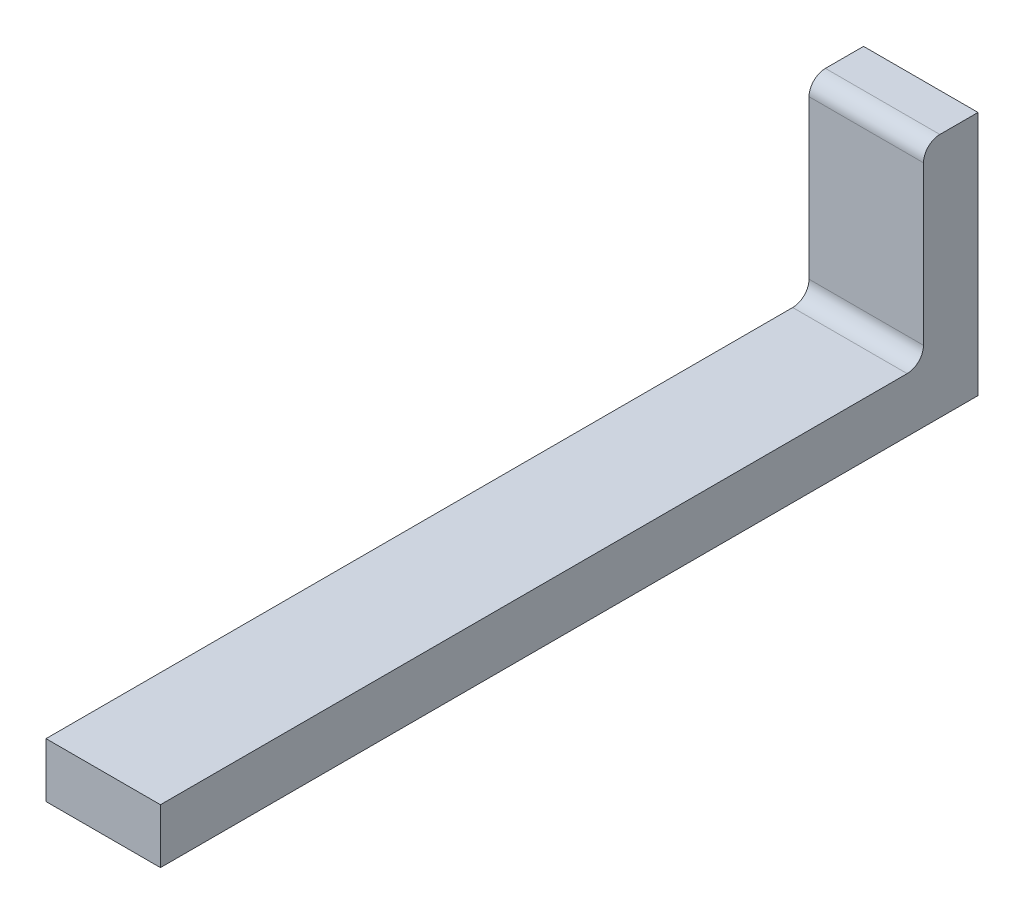
SolidWorks part; units mm, degrees
ref_plane "Front Plane" through (0, 0, 0) normal (0, 0, 1) x (1, 0, 0)
ref_plane "Top Plane" through (0, 0, 0) normal (0, 1, 0) x (1, 0, 0)
ref_plane "Right Plane" through (0, 0, 0) normal (1, 0, 0) x (0, 0, -1)
sketch "Sketch1" plane through (0, 0, 0) normal (0, 1, 0) x (1, 0, 0)
  line L1 (-41, -75) -> (41, -75)
  line L2 (-41, -75) -> (-41, 75)
  line L3 (-41, 75) -> (41, 75)
  line L4 (41, -75) -> (41, 75)
  line L5 (-41, -75) -> (41, 75) construction
  line L6 (-41, 75) -> (41, -75) construction
  point P0 (0, 0)
  dimension "D1" = 82
  dimension "D2" = 150
extrude "Boss-Extrude1" add sketch "Sketch1" along normal blind 10
sketch "Sketch2" plane through (41, 0, 0) normal (1, 0, 0) x (0, 0, -1)
  line L1 (75, 0) -> (65, 0)
  line L2 (75, 0) -> (75, 45)
  line L3 (75, 45) -> (65, 45)
  line L4 (65, 0) -> (65, 45)
  dimension "D1" = 10
  dimension "D2" = 45
extrude "Boss-Extrude2" add sketch "Sketch2" against normal through all
sketch "Sketch3" plane through (0, 0, -65) normal (0, 0, 1) x (1, 0, 0)
  line L0 (-41, 45) -> (41, 45) construction
  line L2 (10, 45) -> (10, 10)
  line L3 (10, 10) -> (20, 10)
  line L4 (20, 45) -> (20, 10)
  line L5 (-41, 10) -> (41, 10) construction
  line L6 (41, 45) -> (41, 10) construction
  line L7 (0, -55) -> (0, 55) construction
  line L9 (10, 45) -> (10, 87)
  line L10 (10, 87) -> (20, 87)
  line L11 (20, 45) -> (20, 87)
  line L12 (-10, 45) -> (-10, 87)
  line L13 (-10, 87) -> (-20, 87)
  line L14 (-20, 45) -> (-20, 87)
  line L15 (-20, 45) -> (-20, 10)
  line L16 (-10, 10) -> (-20, 10)
  line L17 (-10, 45) -> (-10, 10)
  dimension "D1" = 21
  dimension "D2" = 10
  dimension "D3" = 42
extrude "Boss-Extrude3" add sketch "Sketch3" along normal blind 42 and the other way blind 10
fillet "Fillet3" 2 edges at (15, 87, -23) (15, 87, -75) type full round first side face at (15, 48.5, -23) second side face at (0, 51.5, -75) middle face at (15, 87, -49)
fillet "Fillet4" 2 edges at (-15, 87, -23) (-15, 87, -75) type full round first side face at (-15, 48.5, -23) second side face at (0, 47.1667, -75) middle face at (-15, 87, -49)
sketch "Sketch4" plane through (20, 0, 0) normal (1, 0, 0) x (0, 0, -1)
  line L0 (23, 10) -> (23, 50)
  line L1 (23, 10) -> (23, 61) construction
  line L2 (23, 50) -> (-75, 25)
  line L3 (-75, 25) -> (-75, 10)
  line L4 (-75, 10) -> (23, 10)
  dimension "D1" = 15
  dimension "D2" = 40
extrude "Boss-Extrude4" add sketch "Sketch4" against normal up to surface (10 mm away) up to face at (10, 43, -54.3333)
sketch "Sketch5" plane through (-20, 0, 0) normal (-1, 0, 0) x (0, 0, 1)
  line L0 (-23, 50) -> (75, 25)
  line L1 (75, 25) -> (75, 10)
  line L2 (75, 10) -> (-23, 10)
  line L3 (-23, 10) -> (-23, 50)
extrude "Boss-Extrude5" add sketch "Sketch5" against normal up to surface (10 mm away) up to face at (-10, 43, -54.3333)
fillet "Fillet5" radius 15 1 edges at (15, 25, 75)
fillet "Fillet6" radius 15 1 edges at (-15, 25, 75)
sketch "Sketch6" plane through (20, 0, 0) normal (1, 0, 0) x (0, 0, -1)
  line L0 (65, 10) -> (-75, 10) construction
  line L1 (-75, 10) -> (-75, 0) construction
  circle A0 centre (49, 61) radius 8
  circle A1 centre (-60, 17.5) radius 5.5
  dimension "D1" = 7.5
  dimension "D3" = 11
  dimension "D2" = 15
extrude "Cut-Extrude1" cut sketch "Sketch6" against normal through all
fillet "Fillet7" radius 3 1 edges at (30.5, 45, -65)
fillet "Fillet8" radius 3 1 edges at (0, 45, -65)
fillet "Fillet9" radius 3 1 edges at (-30.5, 45, -65)
fillet "Fillet10" radius 3 3 edges at (-30.5, 10, -65) (0, 10, -65) (30.5, 10, -65)
fillet "Fillet11" radius 2 2 edges at (-15, 50, -23) (15, 50, -23)
sketch "Sketch7" plane through (0, 10, 0) normal (0, 1, 0) x (1, 0, 0)
  line L0 (20, 75) -> (41, 75) construction
  line L1 (20, 62) -> (20, -75) construction
  line L3 (20, 21.4944) -> (20, -63.7078) construction
  line L4 (0, -55) -> (0, 55) construction
  circle A0 centre (31.5, 45) radius 5.5
  circle A1 centre (31.5, -15) radius 5.5
  circle A2 centre (-31.5, -15) radius 5.5
  circle A3 centre (-31.5, 45) radius 5.5
  dimension "D1" = 30
  dimension "D3" = 11
  dimension "D4" = 11.5
  dimension "D6" = 11
  dimension "D2" = 11.5
  dimension "D5" = 60
extrude "Cut-Extrude2" cut sketch "Sketch7" against normal through all
ref_plane "Plane1" through (10, 0, 0) normal (-1, 0, 0) x (0, 0, 1)
ref_plane "Plane2" through (-20, 0, 0) normal (-1, 0, 0) x (0, 0, 1)
sketch "Sketch8" plane through (-20, 0, 0) normal (-1, 0, 0) x (0, 0, 1)
  line L1 (-91.2795, 99.075) -> (91.6521, 99.075)
  line L2 (-91.2795, 99.075) -> (-91.2795, -4.4993)
  line L3 (-91.2795, -4.4993) -> (91.6521, -4.4993)
  line L4 (91.6521, 99.075) -> (91.6521, -4.4993)
extrude "Cut-Extrude3" cut sketch "Sketch8" against normal through all
sketch "Sketch9" plane through (0, 10, 0) normal (0, 1, 0) x (1, 0, 0)
  line L1 (-37.5131, 52.3789) -> (-24.8019, 52.3789)
  line L2 (-37.5131, 52.3789) -> (-37.5131, -36.1612)
  line L3 (-37.5131, -36.1612) -> (-24.8019, -36.1612)
  line L4 (-24.8019, 52.3789) -> (-24.8019, -36.1612)
extrude "Boss-Extrude6" add sketch "Sketch9" against normal through all
